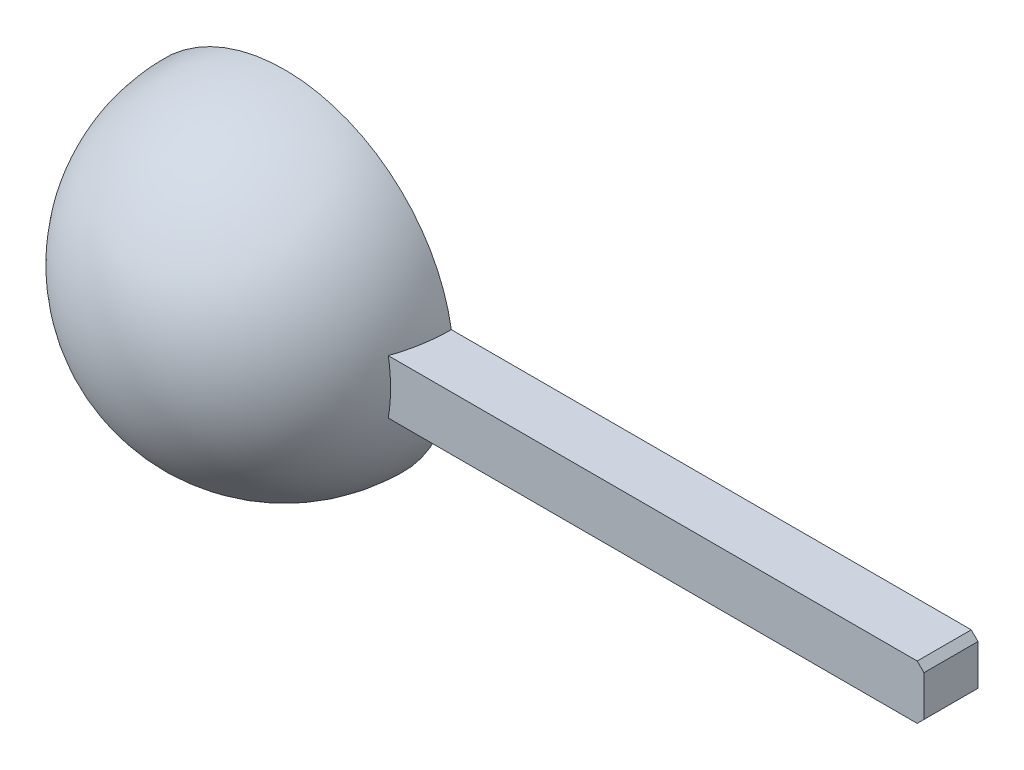
SolidWorks part; units mm, degrees
ref_plane "Plan de face" through (0, 0, 0) normal (0, 0, 1) x (1, 0, 0)
ref_plane "Plan de dessus" through (0, 0, 0) normal (0, 1, 0) x (1, 0, 0)
ref_plane "Plan de droite" through (0, 0, 0) normal (1, 0, 0) x (0, 0, -1)
sketch "Esquisse1" plane through (0, 0, 0) normal (0, 0, 1) x (1, 0, 0)
  line L0 (-25, 0) -> (25, 0)
  arc A0 (-25, 0) -> (25, 0) centre (0, 0) cw
  dimension "D1" = 25
revolve "Révolution1" add sketch "Esquisse1" angle 180 about L0
shell "Coque1" thickness 2 removed face at (-25, 0, 0)
sketch "Esquisse2" plane through (0, 0, 0) normal (0, 0, 1) x (1, 0, 0)
  line L0 (22.6495, 4) -> (102.6495, 4)
  line L1 (102.6495, 4) -> (102.6495, -4)
  line L2 (102.6495, -4) -> (22.6495, -4)
  line L3 (22.6495, -4) -> (22.6495, 4)
  circle A0 centre (0, 0) radius 23 construction
  dimension "D1" = 4
  dimension "D2" = 4
  dimension "D3" = 80
extrude "Boss.-Extru.1" add sketch "Esquisse2" along normal blind 8 contours L2 L3 L0 L1
chamfer "Chanfrein1" distance 1 angle 45 2 edges at (102.6495, 4, 4) (102.6495, -4, 4)
